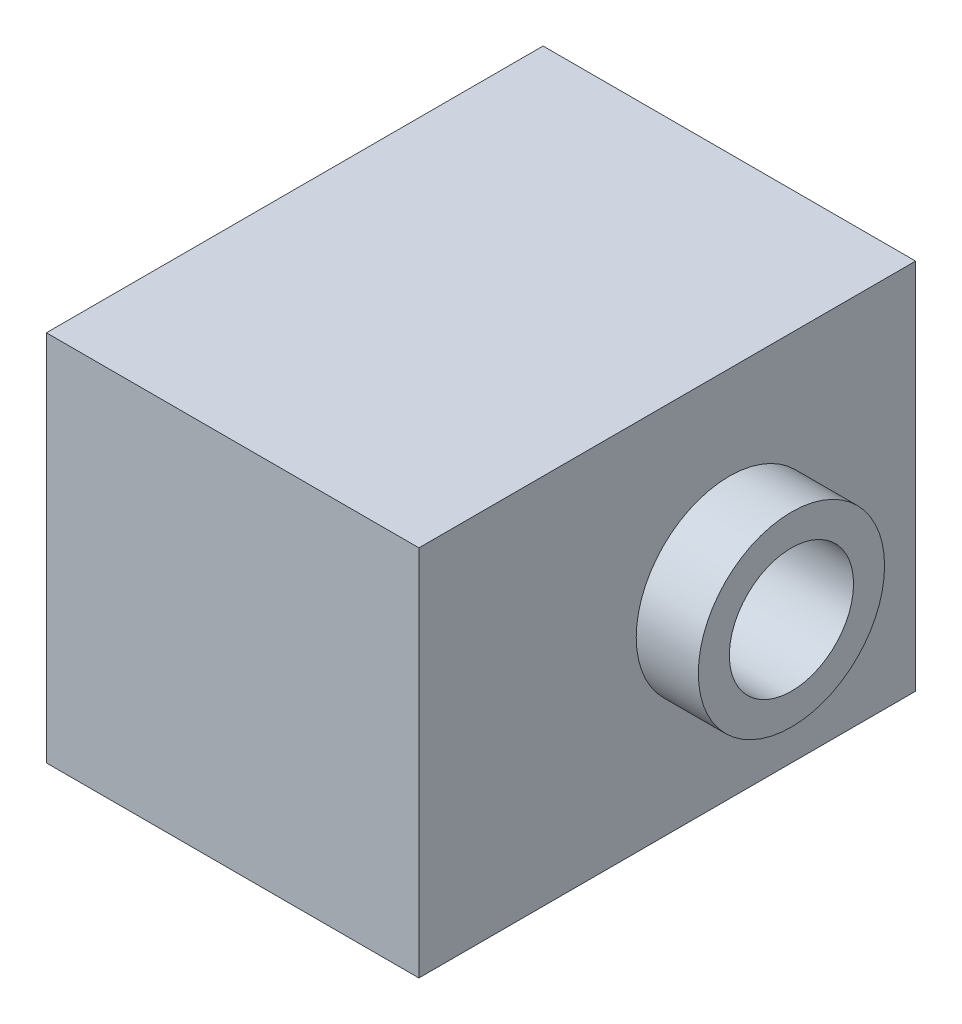
SolidWorks part; units mm, degrees
ref_plane "Спереди" through (0, 0, 0) normal (0, 0, 1) x (1, 0, 0)
ref_plane "Сверху" through (0, 0, 0) normal (0, 1, 0) x (1, 0, 0)
ref_plane "Справа" through (0, 0, 0) normal (1, 0, 0) x (0, 0, -1)
sketch "Эскиз1" plane through (0, 0, 0) normal (1, 0, 0) x (0, 0, -1)
  line L1 (20, -15) -> (-20, -15)
  line L2 (20, -15) -> (20, 15)
  line L3 (20, 15) -> (-20, 15)
  line L4 (-20, -15) -> (-20, 15)
  line L5 (20, -15) -> (-20, 15) construction
  line L6 (20, 15) -> (-20, -15) construction
  point P0 (0, 0)
  dimension "D1" = 40
  dimension "D2" = 30
extrude "Бобышка-Вытянуть1" add sketch "Эскиз1" against normal blind 30
sketch "Эскиз2" plane through (0, 0, 0) normal (1, 0, 0) x (0, 0, -1)
  circle A0 centre (5, 0) radius 5
  circle A1 centre (5, 0) radius 7.5
  point P3 (0, 0)
  dimension "D2" = 10
  dimension "D3" = 15
  dimension "D1" = 5
extrude "Бобышка-Вытянуть2" add sketch "Эскиз2" along normal blind 5
extrude "Вырез-Вытянуть1" cut sketch "Эскиз2<2>" against normal through all contours A0 region at (0, 0, -5)
sketch "Эскиз2<2>" plane through (0, 0, 0) normal (1, 0, 0) x (0, 0, -1) same geometry as "Эскиз2"
